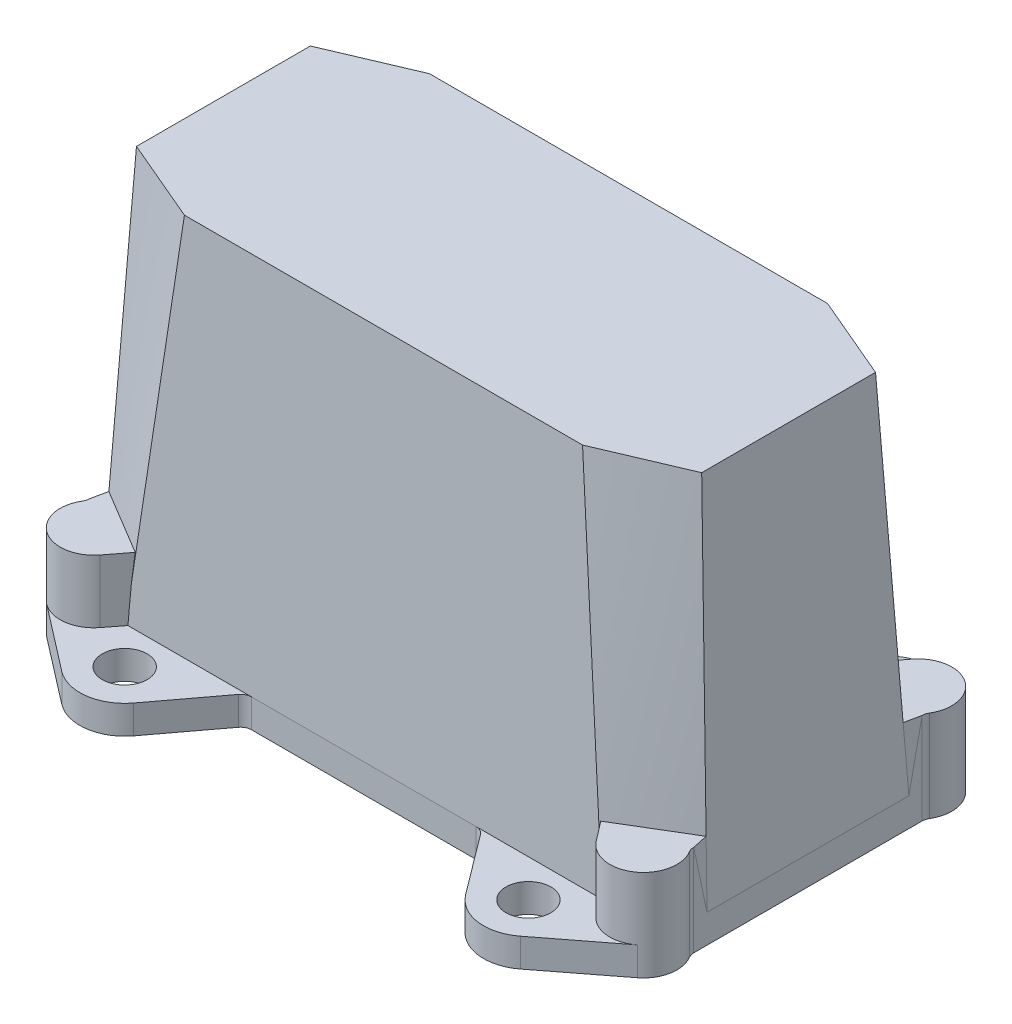
SolidWorks part; units mm, degrees
ref_plane "Front Plane" through (0, 0, 0) normal (0, 0, 1) x (1, 0, 0)
ref_plane "Top Plane" through (0, 0, 0) normal (0, 1, 0) x (1, 0, 0)
ref_plane "Right Plane" through (0, 0, 0) normal (1, 0, 0) x (0, 0, -1)
sketch "Sketch1" plane through (0, 0, 0) normal (0, 1, 0) x (1, 0, 0)
  line L0 (0, 45.3496) -> (0, -45.3496) construction
  line L1 (-18, 16) -> (18, 16) construction
  line L2 (-18, 16) -> (-18, -16) construction
  line L3 (-18, -16) -> (18, -16) construction
  line L4 (18, 16) -> (18, -16) construction
  line L5 (-18, 16) -> (18, -16) construction
  line L6 (-18, -16) -> (18, 16) construction
  line L8 (-26.925, 12.675) -> (26.925, 12.675)
  line L9 (-26.925, 12.675) -> (-26.925, -12.675)
  line L10 (-26.925, -12.675) -> (26.925, -12.675)
  line L11 (26.925, 12.675) -> (26.925, -12.675)
  circle A0 centre (-18, 16) radius 2
  circle A1 centre (18, 16) radius 2
  circle A2 centre (-18, -16) radius 2
  circle A3 centre (18, -16) radius 2
  point P0 (0, 0)
  point P12 (0, 12.675)
  point P13 (0, 0)
  point P18 (26.925, 0)
  dimension "D1" = 4
  dimension "D2" = 36
  dimension "D3" = 32
  dimension "D4" = 53.85
  dimension "D5" = 25.35
sketch "Sketch2" plane through (0, 0, 0) normal (0, 1, 0) x (1, 0, 0)
  line L1 (-24.5, 12.25) -> (24.5, 12.25) construction
  line L2 (-24.5, 12.25) -> (-24.5, -12.25) construction
  line L3 (-24.5, -12.25) -> (24.5, -12.25) construction
  line L4 (26.925, 12.675) -> (-26.925, 12.675)
  line L5 (-26.925, 12.675) -> (-26.925, -12.675)
  line L6 (-26.925, -12.675) -> (26.925, -12.675)
  line L7 (26.925, -12.675) -> (26.925, 12.675)
  line L8 (26.925, 12.675) -> (-26.925, 12.675)
  line L9 (-26.925, 12.675) -> (-26.925, -12.675)
  line L10 (-26.925, -12.675) -> (26.925, -12.675)
  line L11 (26.925, -12.675) -> (26.925, 12.675)
  line L12 (24.5, 12.25) -> (24.5, -12.25) construction
  circle A0 centre (18, 16) radius 4
  circle A1 centre (18, -16) radius 2
  circle A2 centre (18, -16) radius 2
  circle A3 centre (-18, -16) radius 2
  circle A4 centre (-18, -16) radius 2
  circle A5 centre (18, 16) radius 2
  circle A6 centre (18, 16) radius 2
  circle A7 centre (-18, 16) radius 2
  circle A8 centre (-18, 16) radius 2
  circle A9 centre (18, -16) radius 4
  circle A10 centre (-18, -16) radius 4
  circle A11 centre (-18, 16) radius 4
  circle A12 centre (-24.5, 12.25) radius 3
  circle A13 centre (-24.5, -12.25) radius 3
  circle A14 centre (24.5, -12.25) radius 3
  circle A15 centre (24.5, 12.25) radius 3
  point P28 (0, 12.25)
  point P30 (24.5, 0)
  point P35 (-27.5, 12.25)
  point P36 (27.5, 12.25)
  dimension "D9" = 55
  dimension "D7" = 49
  dimension "D8" = 24.5
  dimension "D1" = 0
  dimension "D2" = 0
  dimension "D3" = 0
  dimension "D4" = 0
  dimension "D5" = 0
  dimension "D6" = 2
sketch "Sketch3" plane through (0, 0, 0) normal (0, 1, 0) x (1, 0, 0)
  line L0 (-10.5, 12.675) -> (10.5, 12.675) construction
  line L1 (26.925, 12.675) -> (-26.925, 12.675) construction
  line L2 (-10.5, 12.675) -> (-14.8017, 18.4022)
  line L3 (10.5, 12.675) -> (14.8017, 18.4022)
  line L4 (-26.925, -12.675) -> (26.925, -12.675)
  line L5 (-26.925, 12.675) -> (-26.925, -12.675)
  line L6 (26.925, 12.675) -> (-26.925, 12.675)
  line L7 (26.925, -12.675) -> (26.925, 12.675)
  line L9 (-26.925, 10.4838) -> (-26.925, -10.4838)
  line L11 (26.925, -10.4838) -> (26.925, 10.4838)
  line L12 (-5.6128, 0) -> (5.6128, 0) construction
  line L13 (-26.3321, 14.6256) -> (-20.4428, 19.1675)
  line L14 (20.4428, 19.1675) -> (26.3321, 14.6256)
  line L15 (20.4428, -19.1675) -> (26.3321, -14.6256)
  line L16 (10.5, -12.675) -> (14.8017, -18.4022)
  line L17 (-10.5, -12.675) -> (-14.8017, -18.4022)
  line L18 (-26.3321, -14.6256) -> (-20.4428, -19.1675)
  line L19 (10.5, 12.675) -> (-10.5, 12.675)
  line L20 (-10.5, -12.675) -> (10.5, -12.675)
  circle A1 centre (-18, 16) radius 2
  circle A2 centre (-18, 16) radius 2
  circle A3 centre (18, 16) radius 2
  circle A4 centre (18, 16) radius 2
  circle A5 centre (-18, -16) radius 2
  circle A6 centre (-18, -16) radius 2
  circle A7 centre (18, -16) radius 2
  circle A8 centre (18, -16) radius 2
  circle A9 centre (-24.5, 12.25) radius 3
  arc A10 (-26.3321, 14.6256) -> (-26.925, 10.4838) centre (-24.5, 12.25) ccw
  circle A11 centre (-18, 16) radius 4
  arc A12 (-14.8017, 18.4022) -> (-20.4428, 19.1675) centre (-18, 16) ccw
  circle A13 centre (-18, -16) radius 4
  arc A14 (-20.4428, -19.1675) -> (-14.8017, -18.4022) centre (-18, -16) ccw
  circle A15 centre (18, -16) radius 4
  arc A16 (14.8017, -18.4022) -> (20.4428, -19.1675) centre (18, -16) ccw
  circle A17 centre (18, 16) radius 4
  arc A18 (20.4428, 19.1675) -> (14.8017, 18.4022) centre (18, 16) ccw
  circle A19 centre (24.5, 12.25) radius 3
  arc A20 (26.925, 10.4838) -> (26.3321, 14.6256) centre (24.5, 12.25) ccw
  circle A21 centre (24.5, -12.25) radius 3
  arc A22 (26.3321, -14.6256) -> (26.925, -10.4838) centre (24.5, -12.25) ccw
  circle A23 centre (-24.5, -12.25) radius 3
  arc A24 (-26.925, -10.4838) -> (-26.3321, -14.6256) centre (-24.5, -12.25) ccw
  point P47 (0, 12.675)
  point P52 (0, 0)
  dimension "D14" = 21
  dimension "D1" = 0
  dimension "D2" = 0
  dimension "D3" = 0
  dimension "D4" = 0
  dimension "D5" = 0
  dimension "D6" = 0
  dimension "D7" = 0
  dimension "D8" = 0
  dimension "D9" = 0
  dimension "D10" = 0
  dimension "D11" = 0
  dimension "D12" = 0
  dimension "D13" = 0
extrude "Boss-Extrude1" add sketch "Sketch3" along normal blind 2.54
fillet "Fillet1" radius 1 8 edges at (-26.925, 1.27, 10.4838) (-26.925, 1.27, -10.4838) (-10.5, 1.27, 12.675) (10.5, 1.27, 12.675) (-10.5, 1.27, -12.675) (26.925, 1.27, 10.4838) (26.925, 1.27, -10.4838) (10.5, 1.27, -12.675)
sketch "Sketch4" plane through (0, 2.54, 0) normal (0, 1, 0) x (1, 0, 0)
  line L0 (26.925, -12.675) -> (26.925, 12.675) construction
  line L1 (-26.925, -12.675) -> (26.925, -12.675) construction
  line L2 (-26.925, 12.675) -> (-26.925, -12.675) construction
  line L3 (26.925, 12.675) -> (-26.925, 12.675) construction
  line L4 (26.925, -12.675) -> (26.925, 12.675) construction
  line L5 (-26.925, -12.675) -> (26.925, -12.675) construction
  line L6 (-26.925, 12.675) -> (-26.925, -12.675) construction
  line L7 (26.925, 12.675) -> (-26.925, 12.675) construction
  line L8 (-21.25, -12.675) -> (21.25, -12.675) construction
  line L9 (26.925, 9) -> (26.925, -9) construction
  line L10 (-26.925, -9) -> (-21.25, -12.675)
  line L11 (21.25, -12.675) -> (26.925, -9)
  line L12 (-5.6128, 0) -> (5.6128, 0) construction
  line L13 (-5.6128, 0) -> (5.6128, 0) construction
  line L14 (21.25, 12.675) -> (26.925, 9)
  line L15 (-26.925, 9) -> (-21.25, 12.675)
  line L16 (-26.925, 9) -> (-26.925, -9)
  line L17 (-21.25, -12.675) -> (21.25, -12.675)
  line L18 (26.925, -9) -> (26.925, 9)
  line L19 (21.25, 12.675) -> (-21.25, 12.675)
  point P6 (0, -12.675)
  point P10 (26.925, 0)
  point P11 (-26.925, -9)
  dimension "D1" = 42.5
  dimension "D2" = 18
ref_plane "Plane1" through (0, 35, 0) normal (0, 1, 0) x (1, 0, 0)
sketch "Sketch5" plane through (0, 35, 0) normal (0, 1, 0) x (1, 0, 0)
  line L0 (26.925, -12.675) -> (26.925, 12.675) construction
  line L1 (-26.925, -12.675) -> (26.925, -12.675) construction
  line L2 (26.925, 12.675) -> (-26.925, 12.675) construction
  line L3 (-26.925, 12.675) -> (-26.925, -12.675) construction
  line L4 (26.925, -12.675) -> (26.925, 12.675) construction
  line L5 (-26.925, -12.675) -> (26.925, -12.675) construction
  line L6 (26.925, 12.675) -> (-26.925, 12.675) construction
  line L7 (-26.925, 12.675) -> (-26.925, -12.675) construction
  line L8 (-17.75, -10.925) -> (17.75, -10.925)
  line L9 (-25.2, 10.925) -> (25.2, 10.925) construction
  line L10 (-25.2, 10.925) -> (-25.2, -10.925) construction
  line L11 (-25.2, -10.925) -> (25.2, -10.925) construction
  line L12 (25.2, 10.925) -> (25.2, -10.925) construction
  line L13 (25.2, 7.75) -> (25.2, -7.75) construction
  line L14 (-25.2, -7.75) -> (-17.75, -10.925)
  line L15 (17.75, -10.925) -> (25.2, -7.75)
  line L16 (-5.6128, 0) -> (5.6128, 0) construction
  line L17 (-5.6128, 0) -> (5.6128, 0) construction
  line L18 (17.75, 10.925) -> (25.2, 7.75)
  line L19 (-25.2, 7.75) -> (-17.75, 10.925)
  line L20 (-25.2, 7.75) -> (-25.2, -7.75)
  line L21 (-17.75, 10.925) -> (17.75, 10.925)
  line L22 (25.2, 7.75) -> (25.2, -7.75)
  point P8 (0, 10.925)
  point P10 (25.2, 0)
  point P13 (0, -10.925)
  point P16 (25.2, 0)
  point P17 (-25.2, -7.75)
  dimension "D1" = 50.4
  dimension "D2" = 21.85
  dimension "D3" = 35.5
  dimension "D4" = 15.5
loft "Loft1" add profiles "Sketch4", "Sketch5" connector at (-26.925, 2.54, 9) connector at (-25.2, 35, 7.75)
sketch "Sketch7" plane through (0, 2.54, 0) normal (0, 1, 0) x (1, 0, 0)
  line L5 (-8.4767, 0) -> (8.4767, 0) construction
  line L6 (0, 6.6525) -> (0, -6.6525) construction
  line L7 (-22.1244, -14.0821) -> (-20.2923, -11.7065)
  line L8 (-26.925, 10.1838) -> (-26.925, 9) construction
  line L9 (-26.925, 10.1838) -> (-26.925, 6.5913)
  line L10 (-20.2923, 11.7065) -> (-26.925, 6.5913)
  line L11 (-20.2923, -11.7065) -> (-26.925, -6.5913)
  line L14 (-22.1244, 14.0821) -> (-20.2923, 11.7065)
  line L15 (-20.4428, 19.1675) -> (-26.3321, 14.6256) construction
  line L16 (-26.925, -10.1838) -> (-26.925, -6.5913)
  line L17 (26.925, -10.1838) -> (26.925, -6.5913)
  line L18 (20.2923, -11.7065) -> (26.925, -6.5913)
  line L19 (22.1244, -14.0821) -> (20.2923, -11.7065)
  line L20 (22.1244, 14.0821) -> (20.2923, 11.7065)
  line L21 (20.2923, 11.7065) -> (26.925, 6.5913)
  line L22 (26.925, 10.1838) -> (26.925, 6.5913)
  circle A3 centre (-24.5, 12.25) radius 3 construction
  arc A7 (-22.1244, 14.0821) -> (-27.0688, 10.7003) centre (-24.5, 12.25) ccw
  arc A8 (-26.925, 10.1838) -> (-27.0688, 10.7003) centre (-27.925, 10.1838) ccw construction
  arc A9 (-26.925, 10.1838) -> (-27.0688, 10.7003) centre (-27.925, 10.1838) ccw
  arc A12 (-26.925, -10.1838) -> (-27.0687, -10.7003) centre (-27.925, -10.1838) cw
  arc A13 (-22.1244, -14.0821) -> (-27.0687, -10.7003) centre (-24.5, -12.25) cw
  arc A14 (22.1244, -14.0821) -> (27.0687, -10.7003) centre (24.5, -12.25) ccw
  arc A15 (26.925, -10.1838) -> (27.0687, -10.7003) centre (27.925, -10.1838) ccw
  arc A16 (26.925, 10.1838) -> (27.0687, 10.7003) centre (27.925, 10.1838) cw
  arc A17 (22.1244, 14.0821) -> (27.0687, 10.7003) centre (24.5, 12.25) cw
  point P4 (0, 0)
  point P5 (0, 0)
extrude "Boss-Extrude2" add sketch "Sketch7" along normal blind 8.15 from surface starting at plane "Top Plane"
sketch "Sketch8" plane through (26.9838, 1.434, 0) normal (0.9986, 0.0531, 0) x (0, 0, -1)
  line L1 (-9, 1.1076) -> (9, 1.1076)
  line L2 (-8.784, 6.7255) -> (-7.75, 33.6134) construction
  line L3 (-9, 1.1076) -> (-7.75, 33.6134)
  line L4 (8.784, 6.7255) -> (7.75, 33.6134) construction
  line L5 (9, 1.1076) -> (7.75, 33.6134)
  line L6 (-6.5913, 1.1076) -> (6.5913, 1.1076) construction
  line L7 (-7.75, 33.6134) -> (7.75, 33.6134)
extrude "Cut-Extrude1" cut sketch "Sketch8" along normal through all
ref_plane "Plane2" through (23.9859, 1.0779, -5.1085) normal (0.9771, 0.0439, -0.2081) x (-0.2079, -0.0093, -0.9781)
sketch "Sketch9" plane through (23.9859, 1.0779, -5.1085) normal (0.9771, 0.0439, -0.2081) x (-0.2079, -0.0093, -0.9781)
  line L0 (-15.6346, 6.933) -> (-14.2035, 6.9464)
  line L1 (-14.2035, 6.9464) -> (-14.4243, 1.3286)
  line L2 (-14.4243, 1.3286) -> (-15.6346, 6.933)
extrude "Cut-Extrude2" cut sketch "Sketch9" along normal up to next
ref_plane "Plane3" through (23.9859, 1.0779, 5.1085) normal (0.9771, 0.0439, 0.2081) x (0.2079, 0.0093, -0.9781)
sketch "Sketch10" plane through (23.9859, 1.0779, 5.1085) normal (0.9771, 0.0439, 0.2081) x (0.2079, 0.0093, -0.9781)
  line L0 (14.4243, 1.3286) -> (15.6346, 6.933)
  line L1 (15.6346, 6.933) -> (14.2035, 6.9464)
  line L2 (14.2035, 6.9464) -> (14.4243, 1.3286)
extrude "Cut-Extrude3" cut sketch "Sketch10" along normal up to next
mirror "Mirror1" about plane through (0, 0, 0) normal (1, 0, 0) of "Cut-Extrude3", "Cut-Extrude1", "Cut-Extrude2"
ref_plane "Plane4" through (0, 0, 12.675) normal (0, 0, 1) x (1, 0, 0)
sketch "Sketch11" plane through (0, 0, 12.675) normal (0, 0, 1) x (1, 0, 0)
  line L0 (-10.0004, 0) -> (10.0004, 0) construction
  line L1 (-3.5, 17) -> (3.5, 17) construction
  line L2 (-3.5, 17) -> (-3.5, 10) construction
  line L3 (-3.5, 10) -> (3.5, 10) construction
  line L4 (3.5, 17) -> (3.5, 10) construction
  line L5 (-3.5, 13.5) -> (3.5, 13.5) construction
  circle A0 centre (0, 13.5) radius 1.8
  point P4 (0, 10)
  dimension "D4" = 3.6
  dimension "D1" = 10
  dimension "D2" = 7
  dimension "D3" = 7
ref_plane "Plane5" through (0, 0, -20) normal (0, 0, -1) x (-1, 0, 0)
ref_plane "Plane6" through (0, 0, 20) normal (0, 0, 1) x (1, 0, 0)
ref_plane "Plane7" through (0, 0, -12.675) normal (0, 0, -1) x (-1, 0, 0)
